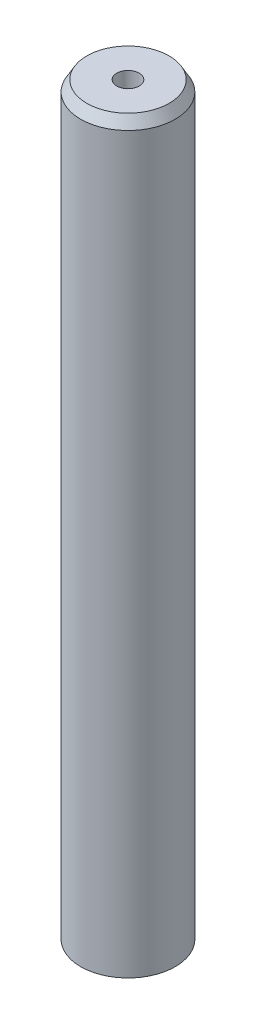
SolidWorks part; units mm, degrees
ref_plane "Front Plane" through (0, 0, 0) normal (0, 0, 1) x (1, 0, 0)
ref_plane "Top Plane" through (0, 0, 0) normal (0, 1, 0) x (1, 0, 0)
ref_plane "Right Plane" through (0, 0, 0) normal (1, 0, 0) x (0, 0, -1)
sketch "Sketch1" plane through (0, 0, 0) normal (0, 1, 0) x (1, 0, 0)
  circle A0 centre (0, 0) radius 5
  dimension "SHAFT_OD" = 10
extrude "Boss-Extrude1" add sketch "Sketch1" along normal blind 79.3357
sketch "Sketch2" plane through (0, 0, 0) normal (0, 1, 0) x (1, 0, 0)
  circle A0 centre (0, 0) radius 1.1851
  dimension "BORE_D" = 2.3702
extrude "Cut-Extrude1" cut sketch "Sketch2" along normal through all
chamfer "Chamfer1" distance 1.1266 angle 30 2 edges at (0, 79.3357, 5) (0, 0, 5) first distance on face at (0, 79.3357, 5) first distance on face at (0, 0, 1.1851)
